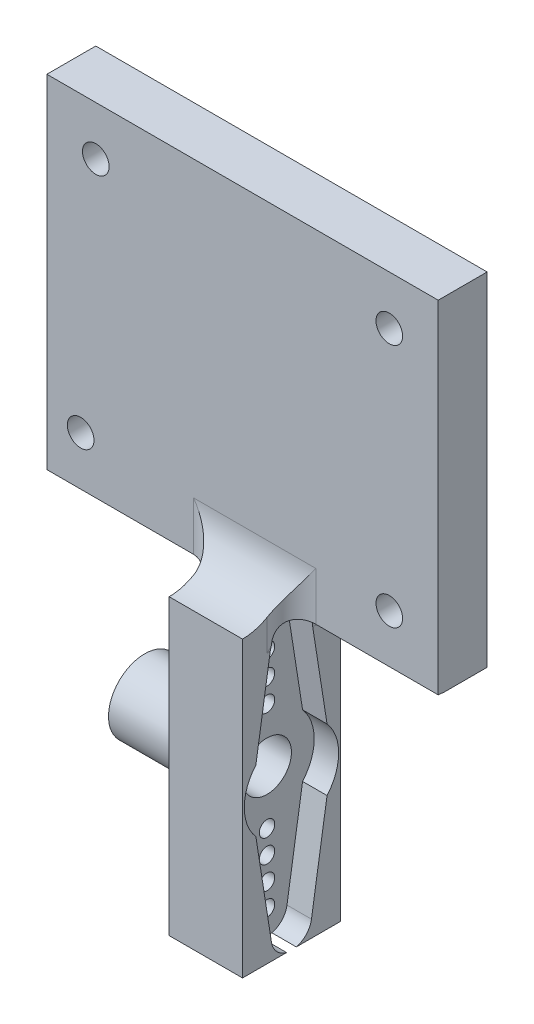
SolidWorks part; units mm, degrees
ref_plane "Front Plane" through (0, 0, 0) normal (0, 0, 1) x (1, 0, 0)
ref_plane "Top Plane" through (0, 0, 0) normal (0, 1, 0) x (1, 0, 0)
ref_plane "Right Plane" through (0, 0, 0) normal (1, 0, 0) x (0, 0, -1)
sketch "Sketch2" plane through (0, 0, 0) normal (1, 0, 0) x (0, 0, -1)
  line L0 (0, 0) -> (36.5165, 0) construction
  line L1 (-6.35, -19.05) -> (6.35, -19.05)
  line L2 (-6.35, -19.05) -> (-6.35, 19.05)
  line L3 (-6.35, 19.05) -> (6.35, 19.05)
  line L4 (6.35, -19.05) -> (6.35, 19.05)
  line L5 (-6.35, -19.05) -> (6.35, 19.05) construction
  line L6 (-6.35, 19.05) -> (6.35, -19.05) construction
  circle A0 centre (0, 0) radius 3.175
  point P0 (0, 0)
  dimension "D3" = 6.35
  dimension "D1" = 12.7
  dimension "D2" = 38.1
extrude "Boss-Extrude1" add sketch "Sketch2" along normal blind 9.525
sketch "Sketch3" plane through (0, 0, 0) normal (-1, 0, 0) x (0, 0, 1)
  circle A0 centre (0, 0) radius 4.699
  dimension "D1" = 9.398
extrude "Boss-Extrude2" add sketch "Sketch3" along normal blind 9.525
ref_plane "Plane1" through (3.175, 0, 0) normal (1, 0, 0) x (0, 0, -1)
sketch "Sketch6" plane through (3.175, 0, 0) normal (1, 0, 0) x (0, 0, -1)
  line L0 (6.35, 19.05) -> (-6.35, 19.05) construction
  line L1 (0, 19.05) -> (6.35, 19.05)
  line L2 (0, 19.05) -> (0, 63.5)
  line L3 (0, 63.5) -> (6.35, 63.5)
  line L4 (6.35, 19.05) -> (6.35, 63.5)
  dimension "D1" = 6.35
  dimension "D2" = 63.5
extrude "Boss-Extrude3" add sketch "Sketch6" along normal mid plane 50.8
fillet "Fillet1" radius 6.35 1 edges at (4.7625, 19.05, 0)
fillet "Fillet4" radius 3.175 4 edges at (0, 22.225, 0) (9.525, 22.225, 0) (9.525, 19.05, -3.175) (0, 19.05, -3.175)
sketch "Sketch7" plane through (9.525, 0, 0) normal (1, 0, 0) x (0, 0, -1)
  line L16 (2.5951, -16.9078) -> (4.6198, -4.0247)
  line L17 (-4.6198, -4.0247) -> (-2.5951, -16.9078)
  line L18 (-2.5951, 16.9078) -> (-4.6198, 4.0247)
  line L19 (4.6198, 4.0247) -> (2.5951, 16.9078)
  line L20 (2.5951, -16.9078) -> (4.6198, -4.0247)
  line L21 (-4.6198, -4.0247) -> (-2.5951, -16.9078)
  line L22 (-2.5951, 16.9078) -> (-4.6198, 4.0247)
  line L23 (4.6198, 4.0247) -> (2.5951, 16.9078)
  arc A16 (4.6198, -4.0247) -> (4.6198, 4.0247) centre (0, 0) ccw
  arc A17 (-2.5951, -16.9078) -> (2.5951, -16.9078) centre (0, -16.5) ccw
  arc A18 (-4.6198, 4.0247) -> (-4.6198, -4.0247) centre (0, 0) ccw
  arc A19 (2.5951, 16.9078) -> (-2.5951, 16.9078) centre (0, 16.5) ccw
  arc A20 (4.6198, -4.0247) -> (4.6198, 4.0247) centre (0, 0) ccw
  arc A21 (-2.5951, -16.9078) -> (2.5951, -16.9078) centre (0, -16.5) ccw
  arc A22 (-4.6198, 4.0247) -> (-4.6198, -4.0247) centre (0, 0) ccw
  arc A23 (2.5951, 16.9078) -> (-2.5951, 16.9078) centre (0, 16.5) ccw
  dimension "D1" = 0.127
sketch "Sketch8" plane through (9.525, 0, 0) normal (1, 0, 0) x (0, 0, -1)
  circle A0 centre (0, -16) radius 0.75 construction
  circle A3 centre (0, -13) radius 0.75 construction
  circle A4 centre (0, -10) radius 0.75 construction
  circle A5 centre (0, -7) radius 0.75 construction
  circle A6 centre (0, 16) radius 0.75 construction
  circle A7 centre (0, 13) radius 0.75 construction
  circle A8 centre (0, 10) radius 0.75 construction
  circle A9 centre (0, 7) radius 0.75 construction
  circle A10 centre (0, -16) radius 0.75 construction
  circle A11 centre (0, -13) radius 0.75 construction
  circle A12 centre (0, -10) radius 0.75 construction
  circle A13 centre (0, -7) radius 0.75 construction
  circle A14 centre (0, 16) radius 0.75 construction
  circle A15 centre (0, 13) radius 0.75 construction
  circle A16 centre (0, 10) radius 0.75 construction
  circle A17 centre (0, 7) radius 0.75 construction
  circle A18 centre (0, -16) radius 1.004
  circle A19 centre (0, -13) radius 1.004
  circle A20 centre (0, -10) radius 1.004
  circle A21 centre (0, -7) radius 1.004
  circle A22 centre (0, 16) radius 1.004
  circle A23 centre (0, 13) radius 1.004
  circle A24 centre (0, 10) radius 1.004
  circle A25 centre (0, 7) radius 1.004
extrude "Cut-Extrude1" cut sketch "Sketch7" against normal blind 3.175 and the other way through all
extrude "Cut-Extrude2" cut sketch "Sketch8" against normal through all
sketch "Sketch9" plane through (0, 0, -6.35) normal (0, 0, -1) x (-1, 0, 0)
  line L13 (15.875, 25.4) -> (15.875, 57.15)
  line L14 (3.175, 25.4) -> (15.875, 25.4)
  line L15 (-22.225, 25.4) -> (-12.7, 25.4)
  line L16 (-22.225, 57.15) -> (-22.225, 25.4)
  line L17 (15.875, 57.15) -> (-22.225, 57.15)
  line L18 (15.875, 25.4) -> (15.875, 57.15) construction
  line L19 (3.175, 25.4) -> (15.875, 25.4) construction
  line L20 (-22.225, 25.4) -> (-12.7, 25.4) construction
  line L21 (-22.225, 57.15) -> (-22.225, 25.4) construction
  line L22 (15.875, 57.15) -> (-22.225, 57.15) construction
  circle A0 centre (-22.225, 57.15) radius 1.727
  circle A1 centre (15.875, 57.15) radius 1.727
  circle A2 centre (17.8398, 25.4) radius 1.727
  circle A3 centre (-22.225, 25.4) radius 1.727
  dimension "D2" = 3.454
extrude "Cut-Extrude3" cut sketch "Sketch9" against normal through all
equation "\"tightTol\"= 0.005in"
equation "\"normTol\"= 0.01in"
equation "\"looseTol\"= 0.02in"
equation "\"Fry height\"= 3 / 8"
equation "\"Fry spacing\"= 1 / 2"
equation "\"Potato width\"= \"Fry spacing\" * 4"
equation "\"Potato length\"= 3"
equation "\"D1@Sketch3\"=0.375000in-\"tightTol\""
equation "\"Plate rim width\"= 0.5"
equation "\"D2@Sketch6\"=2.000000in+\"Plate rim width\""
equation "\"D1@Sketch8\"= \"normTol\""
equation "\"D2@Sketch9\"=3.2mm+\"normTol\""
